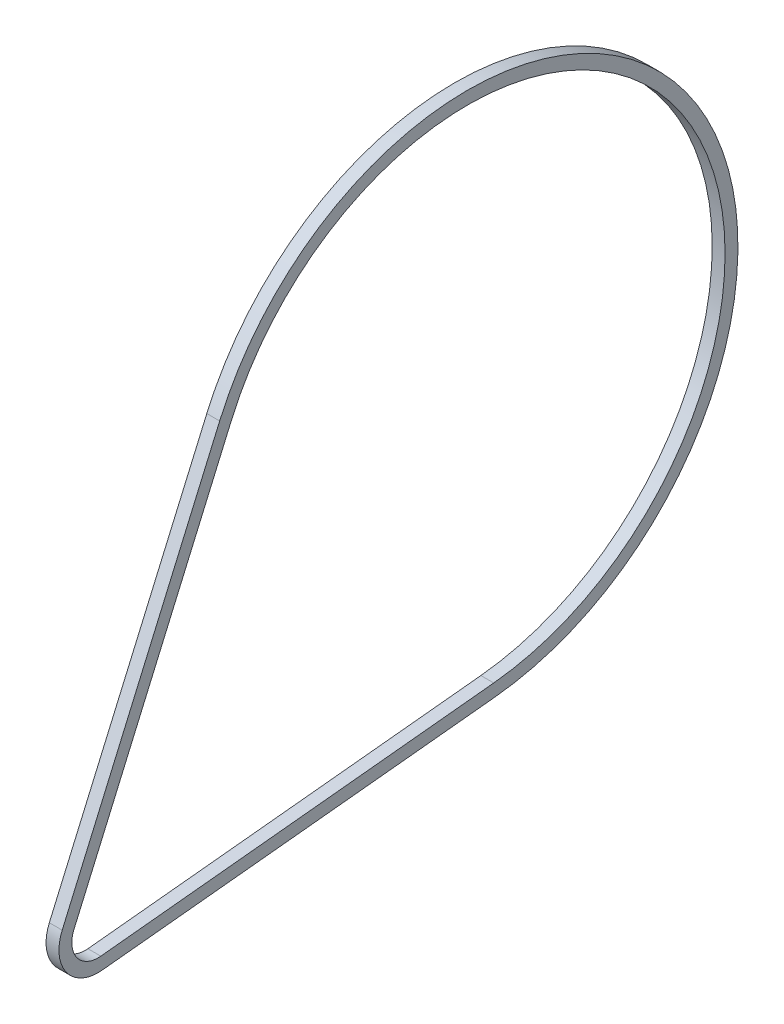
SolidWorks part; units mm, degrees
material "Plain Carbon Steel"
ref_plane "Front Plane" through (0, 0, 0) normal (0, 0, 1) x (1, 0, 0)
ref_plane "Top Plane" through (0, 0, 0) normal (0, 1, 0) x (1, 0, 0)
ref_plane "Right Plane" through (0, 0, 0) normal (1, 0, 0) x (0, 0, -1)
sketch "Sketch1" plane through (0, 0, 0) normal (1, 0, 0) x (0, 0, -1)
  line L0 (244.302, -0.7712) -> (91.683, -16.3531)
  line L2 (76.1803, 4.8544) -> (137.3429, 145.5473)
  line L4 (141.9283, 143.5539) -> (80.7657, 2.861)
  line L6 (91.1752, -11.379) -> (243.7941, 4.2029)
  arc A0 (243.7941, 4.2029) -> (141.9283, 143.5539) centre (233.6373, 103.6858) ccw
  arc A2 (80.7657, 2.861) -> (91.1752, -11.379) centre (90.1373, -1.213) ccw
  arc A3 (244.302, -0.7712) -> (137.3429, 145.5473) centre (233.6373, 103.6858) ccw
  arc A5 (102.2808, 0.5796) -> (102.2448, -3.2348) centre (102.2628, -1.3276) ccw construction
  arc A6 (76.1803, 4.8544) -> (91.683, -16.3531) centre (90.1373, -1.213) ccw
  arc A7 (167.9977, 25.5179) -> (164.3105, 28.7687) centre (165.8517, 26.8003) ccw construction
  dimension "D1" = 5
  dimension "D2" = 5
extrude "Boss-Extrude1" add sketch "Sketch1" along normal blind 5 contours L2 A6 L0 A3 A2 L4 A0 L6 region at (0, -5.1128, -167.6403)
